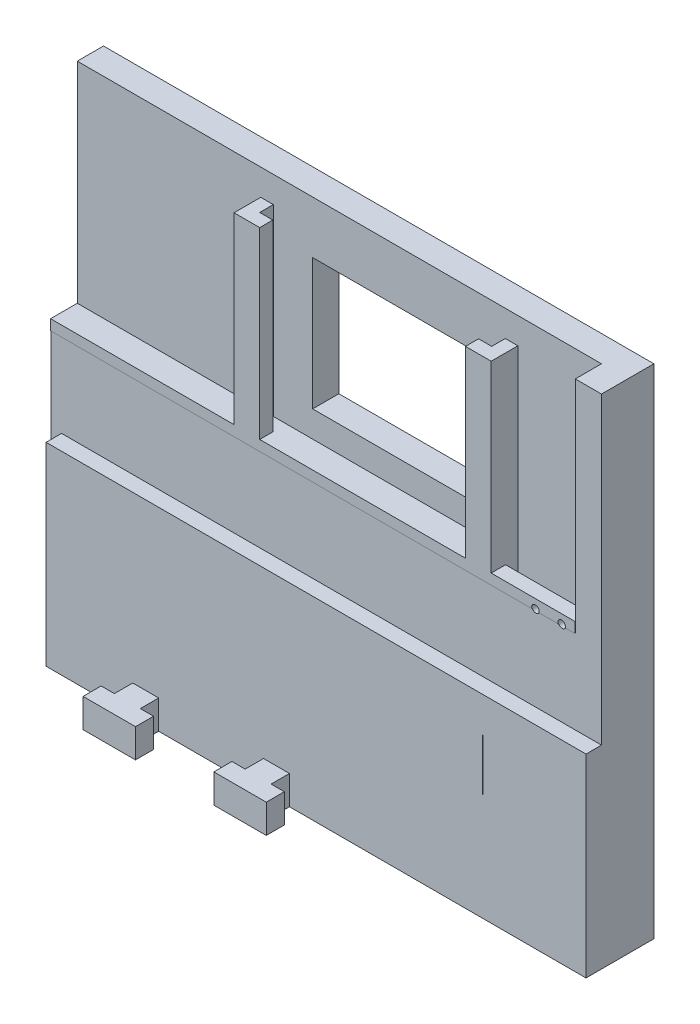
SolidWorks part; units mm, degrees
ref_plane "Front Plane" through (0, 0, 0) normal (0, 0, 1) x (1, 0, 0)
ref_plane "Top Plane" through (0, 0, 0) normal (0, 1, 0) x (1, 0, 0)
ref_plane "Right Plane" through (0, 0, 0) normal (1, 0, 0) x (0, 0, -1)
sketch "Sketch1" plane through (0, 0, 0) normal (0, 0, 1) x (1, 0, 0)
  line L1 (-100, -40) -> (100, -40)
  line L2 (-100, -40) -> (-100, 40)
  line L3 (-100, 40) -> (100, 40)
  line L4 (100, -40) -> (100, 40)
  line L5 (-100, -40) -> (100, 40) construction
  line L6 (-100, 40) -> (100, -40) construction
  point P0 (0, 0)
  dimension "D1" = 0
  dimension "D2" = 200
  dimension "80" = 80
extrude "Boss-Extrude1" add sketch "Sketch1" along normal blind 10
sketch "Sketch2" plane through (0, -40, 0) normal (0, -1, 0) x (1, 0, 0)
  line L0 (-100, 10) -> (100, 10) construction
  line L1 (-30, 10) -> (-25.2, 10)
  line L2 (-30, 10) -> (-30, 15.2)
  line L3 (-30, 15.2) -> (-25.2, 15.2)
  line L4 (-25.2, 10) -> (-25.2, 15.2)
  line L5 (-30, 20.2) -> (-20.2, 20.2)
  line L6 (-30, 20.2) -> (-30, 15.2)
  line L7 (-30, 15.2) -> (-20.2, 15.2)
  line L8 (-20.2, 20.2) -> (-20.2, 15.2)
  line L9 (68.1, 10) -> (63.3, 10)
  line L10 (68.1, 10) -> (68.1, 15.2)
  line L11 (68.1, 15.2) -> (63.3, 15.2)
  line L12 (63.3, 10) -> (63.3, 15.2)
  line L13 (58.3, 20.2) -> (68.1, 20.2)
  line L14 (58.3, 20.2) -> (58.3, 15.2)
  line L15 (58.3, 15.2) -> (68.1, 15.2)
  line L16 (68.1, 20.2) -> (68.1, 15.2)
  line L17 (-100, 10) -> (-100, 0) construction
  dimension "D1" = 0
  dimension "D2" = 0
  dimension "D3" = 0
  dimension "D4" = 5.2
  dimension "D5" = 9.8
  dimension "D6" = 5
  dimension "D7" = 4.8
  dimension "D8" = 9.8
  dimension "D9" = 5
  dimension "D10" = 0
  dimension "D11" = 0
  dimension "D12" = 0
  dimension "D13" = 5.2
  dimension "D14" = 4.8
  dimension "D15" = 88.5
  dimension "D16" = 70
extrude "Boss-Extrude2" add sketch "Sketch2" against normal blind 70 contours L8 L5 L6 L3 L7 | L16 L13 L14 L15 L11 | L4 L3 L2 L1 | L10 L11 L12 L9 region at (-25.1, -40, 17.7) region at (63.2, -40, 17.7)
sketch "Sketch3" plane through (0, 0, 10) normal (0, 0, 1) x (1, 0, 0)
  line L0 (-25.2, -40) -> (63.3, -40) construction
  line L1 (48.3, -30) -> (-10.2, -30)
  line L2 (48.3, -30) -> (48.3, 20)
  line L3 (48.3, 20) -> (-10.2, 20)
  line L4 (-10.2, -30) -> (-10.2, 20)
  line L5 (58.3, 30) -> (58.3, -40) construction
  line L6 (-20.2, 30) -> (-20.2, -40) construction
  line L7 (68.1, 30) -> (63.3, 30) construction
  dimension "D1" = 10
  dimension "D2" = 10
  dimension "D3" = 10
  dimension "D4" = 10
extrude "Cut-Extrude1" cut sketch "Sketch3" against normal blind 10
sketch "Sketch5" plane through (0, -40, 0) normal (0, -1, 0) x (-1, 0, 0)
  line L0 (30, -20.2) -> (20.2, -20.2) construction
  line L1 (100, -20.2) -> (-100, -20.2)
  line L2 (100, -20.2) -> (100, 0)
  line L3 (100, 0) -> (-100, 0)
  line L4 (-100, -20.2) -> (-100, 0)
  line L5 (100, -10) -> (100, 0) construction
  line L7 (100, 0) -> (-100, 0) construction
  line L8 (-100, -10) -> (-100, 0) construction
  dimension "D1" = 0
  dimension "D2" = 0
  dimension "D3" = 0
  dimension "D4" = 0
extrude "Boss-Extrude3" add sketch "Sketch5" along normal blind 4
sketch "Sketch6" plane through (0, 0, 0) normal (0, 0, -1) x (-1, 0, 0)
  line L0 (100, -44) -> (-100, -44) construction
  line L1 (100, -44) -> (-100, -44)
  line L2 (100, -44) -> (100, 40)
  line L3 (100, 40) -> (-100, 40)
  line L4 (-100, -44) -> (-100, 40)
  line L5 (100, -150) -> (-110, -150)
  line L6 (100, -150) -> (100, 40)
  line L7 (100, 40) -> (-110, 40)
  line L8 (-110, -150) -> (-110, 40)
  line L9 (100, 40) -> (100, -44) construction
  line L10 (-100, 40) -> (100, 40) construction
  line L11 (-100, -44) -> (-100, 40) construction
  line M5 (-100, 40) -> (-100, -44)
  line M6 (-100, -44) -> (100, -44)
  line M7 (100, -44) -> (100, 40)
  dimension "D1" = 0
  dimension "D2" = 0
  dimension "D3" = 0
  dimension "D4" = 0
  dimension "D5" = 10
  dimension "D6" = 190
  dimension "D7" = 0
  dimension "D8" = 0
extrude "Boss-Extrude5" add sketch "Sketch6" against normal blind 20 contours L8 L5 L6 L7 M7 M6 M5 region at (8.6364, -93.5455, 0)
sketch "Sketch7" plane through (0, 0, 20) normal (0, 0, 1) x (1, 0, 0)
  line L0 (110, -150) -> (110, 40) construction
  line L1 (110, -76) -> (-96.0009, -76)
  line L2 (110, -76) -> (110, -150)
  line L3 (110, -150) -> (-96.0009, -150)
  line L4 (-96.0009, -76) -> (-96.0009, -150)
  line L5 (70.7614, -89.3834) -> (70.4933, -89.3834)
  line L6 (70.7614, -89.3834) -> (70.7614, -108.9872)
  line L7 (70.7614, -108.9872) -> (70.4933, -108.9872)
  line L8 (70.4933, -89.3834) -> (70.4933, -108.9872)
  line L9 (-100, -150) -> (110, -150) construction
  line L10 (-100, -150) -> (-100, -44) construction
  line L11 (100, -44) -> (-100, -44) construction
  dimension "D1" = 0
  dimension "D2" = 0
  dimension "D3" = 3.9991
  dimension "D4" = 32
extrude "Boss-Extrude6" add sketch "Sketch7" along normal blind 5.9
sketch "Sketch8" plane through (0, -150, 0) normal (0, -1, 0) x (1, 0, 0)
  line L0 (-96.0009, 25.9) -> (110, 25.9) construction
  line L1 (-62.95, 32.9) -> (-53.05, 32.9)
  line L2 (-62.95, 32.9) -> (-62.95, 25.9)
  line L3 (-62.95, 25.9) -> (-53.05, 25.9)
  line L4 (-53.05, 32.9) -> (-53.05, 25.9)
  line L5 (-13.05, 32.9) -> (-3.15, 32.9)
  line L6 (-13.05, 32.9) -> (-13.05, 25.9)
  line L7 (-13.05, 25.9) -> (-3.15, 25.9)
  line L8 (-3.15, 32.9) -> (-3.15, 25.9)
  line L9 (-68, 39.8) -> (-48, 39.8)
  line L10 (-68, 39.8) -> (-68, 32.9)
  line L11 (-68, 32.9) -> (-48, 32.9)
  line L12 (-48, 39.8) -> (-48, 32.9)
  line L13 (-18.1, 39.8) -> (1.9, 39.8)
  line L14 (-18.1, 39.8) -> (-18.1, 32.9)
  line L15 (-18.1, 32.9) -> (1.9, 32.9)
  line L16 (1.9, 39.8) -> (1.9, 32.9)
  line L17 (-100, 20) -> (-100, 0) construction
  line M3 (110, 25.9) -> (-96.0009, 25.9)
  dimension "D1" = 0
  dimension "D2" = 7
  dimension "D3" = 0
  dimension "D4" = 6.9
  dimension "D5" = 20
  dimension "D6" = 9.9
  dimension "D7" = 5.05
  dimension "D8" = 32
  dimension "D9" = 0
  dimension "D10" = 7
  dimension "D11" = 9.9
  dimension "D12" = 0
  dimension "D13" = 20
  dimension "D14" = 6.9
  dimension "D15" = 5.05
  dimension "D16" = 40
extrude "Boss-Extrude7" add sketch "Sketch8" against normal blind 11 contours L12 L9 L10 L11 L1 | L4 L1 L2 M3 | L16 L13 L14 L15 L5 | L8 L5 L6 M3 region at (-58, -150, 36.35) region at (-58, -150, 29.4) region at (-8.1, -150, 29.4) region at (-8.1, -150, 36.35)
sketch "Sketch21" plane through (0, -40, 0) normal (0, 1, 0) x (1, 0, 0)
  line L0 (100, -10) -> (100, -20) construction
  line L1 (100, -14.7) -> (68.1, -14.7)
  line L2 (100, -14.7) -> (100, -10)
  line L3 (100, -10) -> (68.1, -10)
  line L4 (68.1, -14.7) -> (68.1, -10)
  line L5 (68.1, -10) -> (100, -10) construction
  line L6 (68.1, -20.2) -> (68.1, -10) construction
  dimension "D1" = 0
  dimension "D2" = 0
  dimension "D3" = 4.7
  dimension "D4" = 0
extrude "Cut-Extrude7" cut sketch "Sketch21" against normal blind 5.5
sketch "Sketch22" plane through (0, 0, 20.2) normal (0, 0, 1) x (1, 0, 0)
  line L0 (100, -40) -> (68.1, -40) construction
  line L1 (100, -40) -> (100, -44) construction
  circle A0 centre (95, -43.5) radius 1.425
  circle A1 centre (85, -43.5) radius 1.425
  dimension "D1" = 2.85
  dimension "D2" = 2.85
  dimension "D4" = 3.5
  dimension "D3" = 3.5
  dimension "D5" = 5
  dimension "D6" = 10
extrude "Cut-Extrude8" cut sketch "Sketch22" against normal blind 5.5
